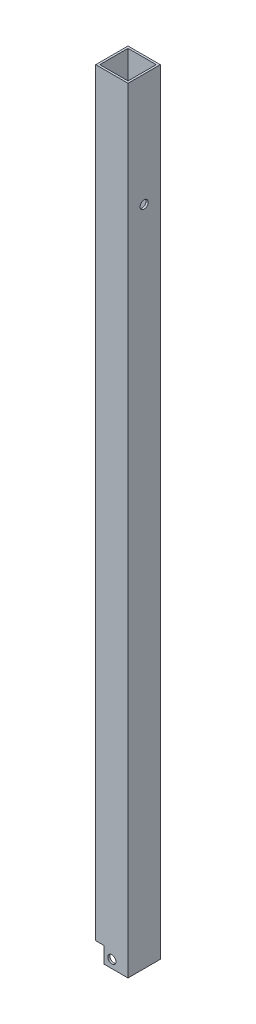
SolidWorks part; units mm, degrees
ref_plane "Front Plane" through (0, 0, 0) normal (0, 0, 1) x (1, 0, 0)
ref_plane "Top Plane" through (0, 0, 0) normal (0, 1, 0) x (1, 0, 0)
ref_plane "Right Plane" through (0, 0, 0) normal (1, 0, 0) x (0, 0, -1)
sketch "Sketch1" plane through (0, 0, 0) normal (0, 1, 0) x (1, 0, 0)
  line L1 (-12.7, -12.7) -> (12.7, -12.7)
  line L2 (-12.7, -12.7) -> (-12.7, 12.7)
  line L3 (-12.7, 12.7) -> (12.7, 12.7)
  line L4 (12.7, -12.7) -> (12.7, 12.7)
  line L5 (-12.7, -12.7) -> (12.7, 12.7) construction
  line L6 (-12.7, 12.7) -> (12.7, -12.7) construction
  line L7 (-11.1125, -11.1125) -> (11.1125, -11.1125)
  line L8 (-11.1125, -11.1125) -> (-11.1125, 11.1125)
  line L9 (-11.1125, 11.1125) -> (11.1125, 11.1125)
  line L10 (11.1125, -11.1125) -> (11.1125, 11.1125)
  line L11 (-11.1125, -11.1125) -> (11.1125, 11.1125) construction
  line L12 (-11.1125, 11.1125) -> (11.1125, -11.1125) construction
  point P0 (0, 0)
  point P6 (0, 0)
  dimension "D1" = 25.4
  dimension "D2" = 25.4
  dimension "D3" = 1.5875
  dimension "D4" = 1.5875
extrude "Boss-Extrude1" add sketch "Sketch1" along normal blind 609.6
sketch "Sketch2" plane through (0, 0, 12.7) normal (0, 0, 1) x (1, 0, 0)
  line L0 (-12.7, 0) -> (12.7, 0) construction
  line L3 (-6.35, 0) -> (-12.7, 0)
  line L4 (-6.35, 0) -> (-6.35, 12.7)
  line L6 (-6.35, 12.7) -> (-12.7, 12.7)
  line L7 (-12.7, 0) -> (-12.7, 12.7)
  line L8 (-12.7, 609.6) -> (-12.7, 0) construction
  line L9 (12.7, 609.6) -> (12.7, 0) construction
  dimension "D1" = 19.05
  dimension "D2" = 12.7
extrude "Cut-Extrude1" cut sketch "Sketch2" against normal blind 25.4
sketch "Sketch3" plane through (0, 0, 12.7) normal (0, 0, 1) x (1, 0, 0)
  line L0 (12.7, 609.6) -> (12.7, 0) construction
  line L1 (-6.35, 0) -> (12.7, 0) construction
  circle A0 centre (0, 6.35) radius 3.175
  dimension "D1" = 6.35
  dimension "D2" = 12.7
  dimension "D3" = 6.35
extrude "Cut-Extrude2" cut sketch "Sketch3" against normal blind 25.4
sketch "Sketch4" plane through (12.7, 0, 0) normal (1, 0, 0) x (0, 0, -1)
  line L0 (-12.7, 609.6) -> (12.7, 609.6) construction
  line L1 (-12.7, 609.6) -> (-12.7, 0) construction
  circle A0 centre (0, 520.7) radius 3.175
  dimension "D1" = 6.35
  dimension "D2" = 88.9
  dimension "D3" = 12.7
extrude "Cut-Extrude3" cut sketch "Sketch4" against normal blind 25.4
